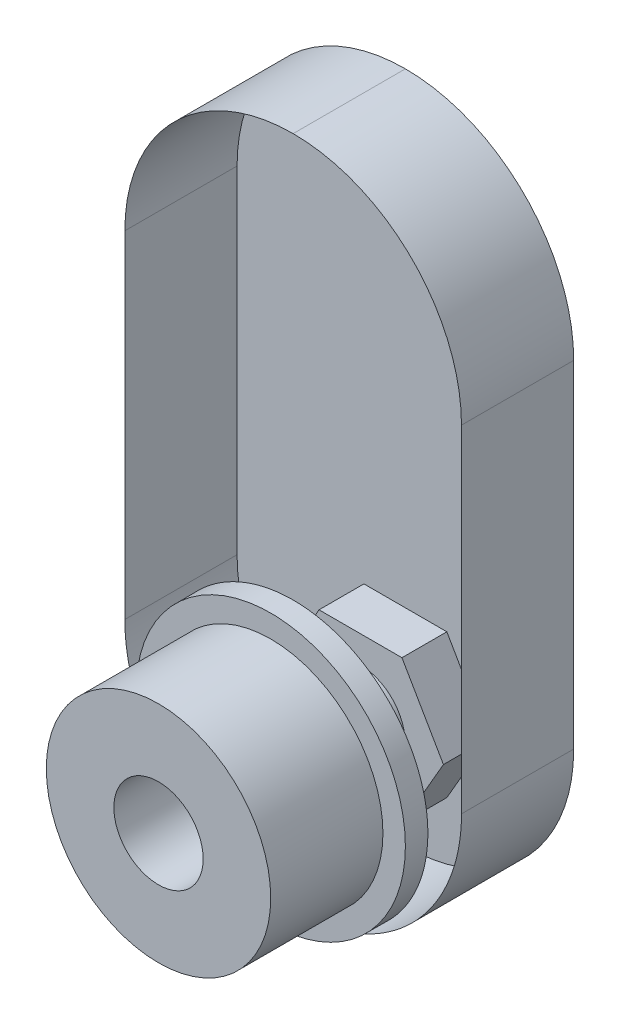
SolidWorks part; units mm, degrees
ref_plane "Front Plane" through (0, 0, 0) normal (0, 0, 1) x (1, 0, 0)
ref_plane "Top Plane" through (0, 0, 0) normal (0, 1, 0) x (1, 0, 0)
ref_plane "Right Plane" through (0, 0, 0) normal (1, 0, 0) x (0, 0, -1)
sketch "Sketch1" plane through (0, 0, 0) normal (0, 0, 1) x (1, 0, 0)
  line L1 (-9.525, 0) -> (9.525, 0)
  line L2 (-9.525, 0) -> (-9.525, 38.1)
  line L3 (-9.525, 38.1) -> (9.525, 38.1)
  line L4 (9.525, 0) -> (9.525, 38.1)
  point P4 (0, 0)
  dimension "D1" = 38.1
  dimension "D2" = 19.05
extrude "Boss-Extrude1" add sketch "Sketch1" along normal blind 6.35
sketch "Sketch2" plane through (0, 0, 6.35) normal (0, 0, 1) x (1, 0, 0)
  line L3 (-9.525, 0) -> (9.525, 0) construction
  circle A0 centre (0, 7.62) radius 6.35
  dimension "D1" = 12.7
  dimension "D2" = 7.62
extrude "Boss-Extrude2" add sketch "Sketch2" along normal blind 7.62
hole_wizard "#8 (0.199) Diameter Hole1" positions "Sketch3" profile "Sketch4" hole size "#8" standard "ANSI Inch" end condition through all
sketch "Sketch3" plane through (0, 0, 13.97) normal (0, 0, 1) x (1, 0, 0)
  circle A0 centre (0, 7.62) radius 6.35 construction
  point P0 (0, 7.62)
sketch "Sketch4" plane through (0, 7.62, 13.97) normal (1, 0, 0) x (0, -1, 0)
  line L0 (0, 0) -> (0, 13.97)
  line L1 (0, 13.97) -> (2.5273, 13.97)
  line L2 (2.5273, 13.97) -> (2.5273, 0)
  line L5 (2.5273, 0) -> (0, 0)
  line L11 (0, -6.35) -> (0, 107.95) construction
  dimension "Thru Hole Dia." = 5.0546
  dimension "Thru Hole Depth" = 13.97
sketch "Sketch5" plane through (0, 0, 0) normal (0, 0, -1) x (-1, 0, 0)
  line L1 (2.3464, 3.556) -> (4.6927, 7.62)
  line L2 (4.6927, 7.62) -> (2.3464, 11.684)
  line L3 (2.3464, 11.684) -> (-2.3464, 11.684)
  line L4 (-2.3464, 11.684) -> (-4.6927, 7.62)
  line L5 (-4.6927, 7.62) -> (-2.3464, 3.556)
  line L6 (-2.3464, 3.556) -> (2.3464, 3.556)
  circle A0 centre (0, 7.62) radius 4.064 construction
  dimension "D1" = 8.128
extrude "Cut-Extrude1" cut sketch "Sketch5" against normal blind 2.54
sketch "Sketch7" plane through (0, 0, 6.35) normal (0, 0, 1) x (1, 0, 0)
  circle A0 centre (0, 7.62) radius 7.62
  circle A1 centre (0, 7.62) radius 6.35
  circle A2 centre (0, 7.62) radius 6.35 construction
  dimension "D1" = 15.24
extrude "Boss-Extrude3" add sketch "Sketch7" along normal blind 1.27
fillet "Fillet1" radius 9.525 4 edges at (9.525, 0, 3.175) (-9.525, 0, 3.175) (9.525, 38.1, 3.175) (-9.525, 38.1, 3.175)
